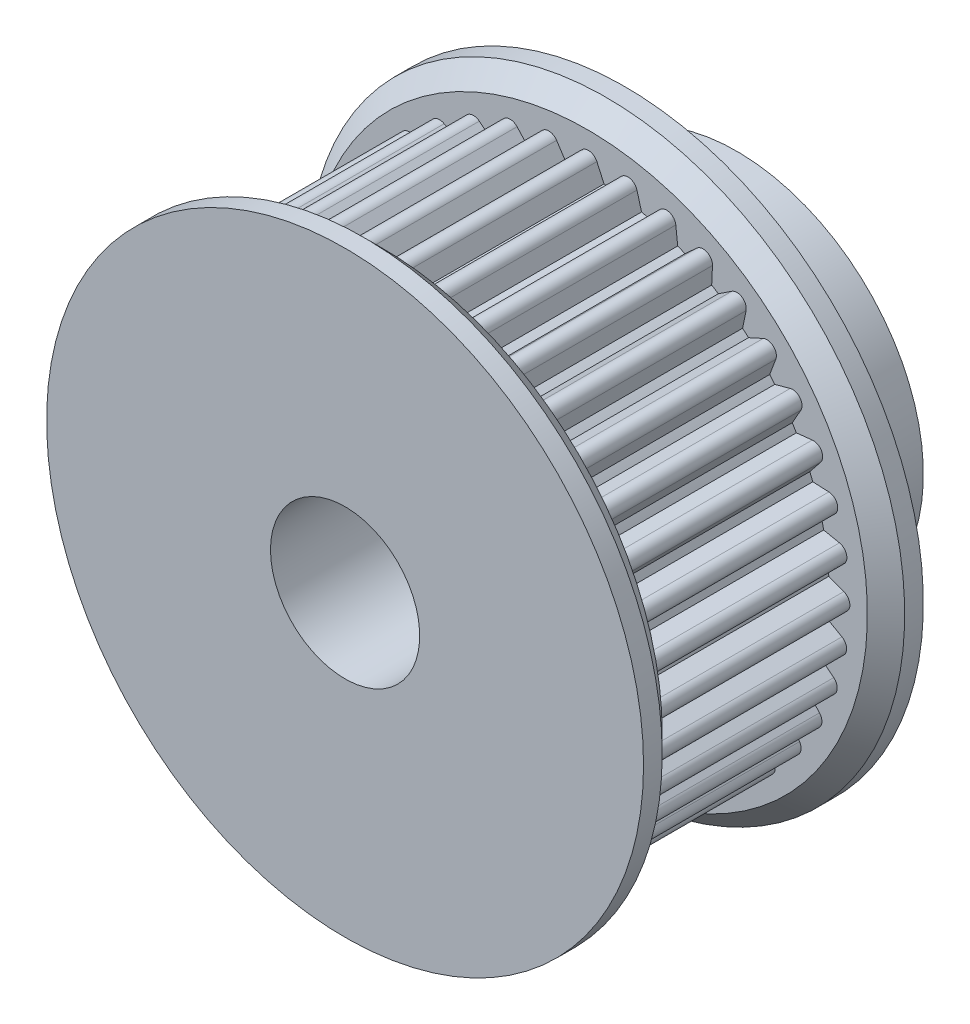
SolidWorks part; units mm, degrees
ref_plane "前视基准面" through (0, 0, 0) normal (0, 0, 1) x (1, 0, 0)
ref_plane "上视基准面" through (0, 0, 0) normal (0, 1, 0) x (1, 0, 0)
ref_plane "右视基准面" through (0, 0, 0) normal (1, 0, 0) x (0, 0, -1)
sketch "草图1" plane through (0, 0, 0) normal (0, 0, 1) x (1, 0, 0)
  line L0 (-0.7281, 12.9295) -> (0, 14.8658)
  line L1 (0, 14.8658) -> (0.8824, 12.9199)
  line L2 (0.8824, 12.9199) -> (-0.7281, 12.9295)
  line L3 (1.3035, 12.8842) -> (2.3255, 14.6827)
  line L4 (2.3255, 14.6827) -> (2.8926, 12.6228)
  line L5 (2.8926, 12.6228) -> (1.3035, 12.8842)
  line L6 (3.303, 12.5217) -> (4.5938, 14.1382)
  line L7 (4.5938, 14.1382) -> (4.8317, 12.0149)
  line L8 (4.8317, 12.0149) -> (3.303, 12.5217)
  line L9 (5.2212, 11.8508) -> (6.7489, 13.2455)
  line L10 (6.7489, 13.2455) -> (6.6517, 11.1111)
  line L11 (6.6517, 11.1111) -> (5.2212, 11.8508)
  line L12 (7.0108, 10.8881) -> (8.7379, 12.0266)
  line L13 (8.7379, 12.0266) -> (8.308, 9.9338)
  line L14 (8.308, 9.9338) -> (7.0108, 10.8881)
  line L15 (8.6277, 9.6574) -> (10.5117, 10.5117)
  line L16 (10.5117, 10.5117) -> (9.7597, 8.5118)
  line L17 (9.7597, 8.5118) -> (8.6277, 9.6574)
  line L18 (10.0323, 8.1888) -> (12.0266, 8.7379)
  line L19 (12.0266, 8.7379) -> (10.9711, 6.8803)
  line L20 (10.9711, 6.8803) -> (10.0323, 8.1888)
  line L21 (11.1897, 6.5186) -> (13.2455, 6.7489)
  line L22 (13.2455, 6.7489) -> (11.9123, 5.0793)
  line L23 (11.9123, 5.0793) -> (11.1897, 6.5186)
  line L24 (12.0717, 4.6879) -> (14.1382, 4.5938)
  line L25 (14.1382, 4.5938) -> (12.5602, 3.1533)
  line L26 (12.5602, 3.1533) -> (12.0717, 4.6879)
  line L27 (12.6564, 2.7417) -> (14.6827, 2.3255)
  line L28 (14.6827, 2.3255) -> (12.8989, 1.1496)
  line L29 (12.8989, 1.1496) -> (12.6564, 2.7417)
  line L30 (12.9295, 0.7281) -> (14.8658, 0)
  line L31 (14.8658, 0) -> (12.9199, -0.8824)
  line L32 (12.9199, -0.8824) -> (12.9295, 0.7281)
  line L33 (12.8842, -1.3035) -> (14.6827, -2.3255)
  line L34 (14.6827, -2.3255) -> (12.6228, -2.8926)
  line L35 (12.6228, -2.8926) -> (12.8842, -1.3035)
  line L36 (12.5217, -3.303) -> (14.1382, -4.5938)
  line L37 (14.1382, -4.5938) -> (12.0149, -4.8317)
  line L38 (12.0149, -4.8317) -> (12.5217, -3.303)
  line L39 (11.8508, -5.2212) -> (13.2455, -6.7489)
  line L40 (13.2455, -6.7489) -> (11.1111, -6.6517)
  line L41 (11.1111, -6.6517) -> (11.8508, -5.2212)
  line L42 (10.8881, -7.0108) -> (12.0266, -8.7379)
  line L43 (12.0266, -8.7379) -> (9.9338, -8.308)
  line L44 (9.9338, -8.308) -> (10.8881, -7.0108)
  line L45 (9.6574, -8.6277) -> (10.5117, -10.5117)
  line L46 (10.5117, -10.5117) -> (8.5118, -9.7597)
  line L47 (8.5118, -9.7597) -> (9.6574, -8.6277)
  line L48 (8.1888, -10.0323) -> (8.7379, -12.0266)
  line L49 (8.7379, -12.0266) -> (6.8803, -10.9711)
  line L50 (6.8803, -10.9711) -> (8.1888, -10.0323)
  line L51 (6.5186, -11.1897) -> (6.7489, -13.2455)
  line L52 (6.7489, -13.2455) -> (5.0793, -11.9123)
  line L53 (5.0793, -11.9123) -> (6.5186, -11.1897)
  line L54 (4.6879, -12.0717) -> (4.5938, -14.1382)
  line L55 (4.5938, -14.1382) -> (3.1533, -12.5602)
  line L56 (3.1533, -12.5602) -> (4.6879, -12.0717)
  line L57 (2.7417, -12.6564) -> (2.3255, -14.6827)
  line L58 (2.3255, -14.6827) -> (1.1496, -12.8989)
  line L59 (1.1496, -12.8989) -> (2.7417, -12.6564)
  line L60 (0.7281, -12.9295) -> (0, -14.8658)
  line L61 (0, -14.8658) -> (-0.8824, -12.9199)
  line L62 (-0.8824, -12.9199) -> (0.7281, -12.9295)
  line L63 (-1.3035, -12.8842) -> (-2.3255, -14.6827)
  line L64 (-2.3255, -14.6827) -> (-2.8926, -12.6228)
  line L65 (-2.8926, -12.6228) -> (-1.3035, -12.8842)
  line L66 (-3.303, -12.5217) -> (-4.5938, -14.1382)
  line L67 (-4.5938, -14.1382) -> (-4.8317, -12.0149)
  line L68 (-4.8317, -12.0149) -> (-3.303, -12.5217)
  line L69 (-5.2212, -11.8508) -> (-6.7489, -13.2455)
  line L70 (-6.7489, -13.2455) -> (-6.6517, -11.1111)
  line L71 (-6.6517, -11.1111) -> (-5.2212, -11.8508)
  line L72 (-7.0108, -10.8881) -> (-8.7379, -12.0266)
  line L73 (-8.7379, -12.0266) -> (-8.308, -9.9338)
  line L74 (-8.308, -9.9338) -> (-7.0108, -10.8881)
  line L75 (-8.6277, -9.6574) -> (-10.5117, -10.5117)
  line L76 (-10.5117, -10.5117) -> (-9.7597, -8.5118)
  line L77 (-9.7597, -8.5118) -> (-8.6277, -9.6574)
  line L78 (-10.0323, -8.1888) -> (-12.0266, -8.7379)
  line L79 (-12.0266, -8.7379) -> (-10.9711, -6.8803)
  line L80 (-10.9711, -6.8803) -> (-10.0323, -8.1888)
  line L81 (-11.1897, -6.5186) -> (-13.2455, -6.7489)
  line L82 (-13.2455, -6.7489) -> (-11.9123, -5.0793)
  line L83 (-11.9123, -5.0793) -> (-11.1897, -6.5186)
  line L84 (-12.0717, -4.6879) -> (-14.1382, -4.5938)
  line L85 (-14.1382, -4.5938) -> (-12.5602, -3.1533)
  line L86 (-12.5602, -3.1533) -> (-12.0717, -4.6879)
  line L87 (-12.6564, -2.7417) -> (-14.6827, -2.3255)
  line L88 (-14.6827, -2.3255) -> (-12.8989, -1.1496)
  line L89 (-12.8989, -1.1496) -> (-12.6564, -2.7417)
  line L90 (-12.9295, -0.7281) -> (-14.8658, 0)
  line L91 (-14.8658, 0) -> (-12.9199, 0.8824)
  line L92 (-12.9199, 0.8824) -> (-12.9295, -0.7281)
  line L93 (-12.8842, 1.3035) -> (-14.6827, 2.3255)
  line L94 (-14.6827, 2.3255) -> (-12.6228, 2.8926)
  line L95 (-12.6228, 2.8926) -> (-12.8842, 1.3035)
  line L96 (-12.5217, 3.303) -> (-14.1382, 4.5938)
  line L97 (-14.1382, 4.5938) -> (-12.0149, 4.8317)
  line L98 (-12.0149, 4.8317) -> (-12.5217, 3.303)
  line L99 (-11.8508, 5.2212) -> (-13.2455, 6.7489)
  line L100 (-13.2455, 6.7489) -> (-11.1111, 6.6517)
  line L101 (-11.1111, 6.6517) -> (-11.8508, 5.2212)
  line L102 (-10.8881, 7.0108) -> (-12.0266, 8.7379)
  line L103 (-12.0266, 8.7379) -> (-9.9338, 8.308)
  line L104 (-9.9338, 8.308) -> (-10.8881, 7.0108)
  line L105 (-9.6574, 8.6277) -> (-10.5117, 10.5117)
  line L106 (-10.5117, 10.5117) -> (-8.5118, 9.7597)
  line L107 (-8.5118, 9.7597) -> (-9.6574, 8.6277)
  line L108 (-8.1888, 10.0323) -> (-8.7379, 12.0266)
  line L109 (-8.7379, 12.0266) -> (-6.8803, 10.9711)
  line L110 (-6.8803, 10.9711) -> (-8.1888, 10.0323)
  line L111 (-6.5186, 11.1897) -> (-6.7489, 13.2455)
  line L112 (-6.7489, 13.2455) -> (-5.0793, 11.9123)
  line L113 (-5.0793, 11.9123) -> (-6.5186, 11.1897)
  line L114 (-4.6879, 12.0717) -> (-4.5938, 14.1382)
  line L115 (-4.5938, 14.1382) -> (-3.1533, 12.5602)
  line L116 (-3.1533, 12.5602) -> (-4.6879, 12.0717)
  line L117 (-2.7417, 12.6564) -> (-2.3255, 14.6827)
  line L118 (-2.3255, 14.6827) -> (-1.1496, 12.8989)
  line L119 (-1.1496, 12.8989) -> (-2.7417, 12.6564)
  circle A0 centre (0, 0) radius 12.95
  point P125 (0, 0)
  dimension "D1" = 25.9
  dimension "D2" = 40
extrude "凸台-拉伸3" add sketch "草图1" along normal blind 11 contours L32 A0 L29 L26 L23 L20 L17 L14 L11 L8 L5 L2 L119 L116 L113 L110 L107 L104 L101 L98 L95 L92 L89 L86 L83 L80 L77 | L72 L73 L74 | L69 L70 L71 | L66 L67 L68 | L63 L64 L65 | L60 L61 L62 | L57 L58 L59 | L54 L55 L56 | L49 L50 L48 | L52 L53 L51 | L46 L47 L45 | L43 L44 L42 | L40 L41 L39 | L37 L38 L36 | L33 L34 L35
fillet "圆角3" radius 0.5 40 edges at (-10.5117, 10.5117, 5.5) (-12.0266, 8.7379, 5.5) (-13.2455, 6.7489, 5.5) (-14.1382, 4.5938, 5.5) (-14.6827, 2.3255, 5.5) (-14.8658, 0, 5.5) (-14.6827, -2.3255, 5.5) (-14.1382, -4.5938, 5.5) (-13.2455, -6.7489, 5.5) (-12.0266, -8.7379, 5.5) (-10.5117, -10.5117, 5.5) (-8.7379, -12.0266, 5.5) (-6.7489, -13.2455, 5.5) (-4.5938, -14.1382, 5.5) (-2.3255, -14.6827, 5.5) (0, -14.8658, 5.5) (2.3255, -14.6827, 5.5) (4.5938, -14.1382, 5.5) (6.7489, -13.2455, 5.5) (8.7379, -12.0266, 5.5) (10.5117, -10.5117, 5.5) (12.0266, -8.7379, 5.5) (13.2455, -6.7489, 5.5) (14.1382, -4.5938, 5.5) (14.6827, -2.3255, 5.5) (14.8658, 0, 5.5) (14.6827, 2.3255, 5.5) (14.1382, 4.5938, 5.5) (13.2455, 6.7489, 5.5) (12.0266, 8.7379, 5.5) (10.5117, 10.5117, 5.5) (8.7379, 12.0266, 5.5) (6.7489, 13.2455, 5.5) (4.5938, 14.1382, 5.5) (2.3255, 14.6827, 5.5) (0, 14.8658, 5.5) (-2.3255, 14.6827, 5.5) (-4.5938, 14.1382, 5.5) (-6.7489, 13.2455, 5.5) (-8.7379, 12.0266, 5.5)
sketch "草图3" plane through (0, 0, 11) normal (0, 0, 1) x (1, 0, 0)
  circle A0 centre (0, 0) radius 16
  dimension "D1" = 32
extrude "凸台-拉伸4" add sketch "草图3" along normal blind 2
sketch "草图4" plane through (0, 0, 0) normal (0, 0, -1) x (-1, 0, 0)
  circle A0 centre (0, 0) radius 16
  dimension "D1" = 32
extrude "凸台-拉伸5" add sketch "草图4" along normal blind 2
chamfer "倒角1" distance 1 angle 45 1 edges at (16, 0, 11)
chamfer "倒角2" distance 1 angle 45 1 edges at (-16, 0, 0)
sketch "草图5" plane through (0, 0, -2) normal (0, 0, -1) x (-1, 0, 0)
  circle A0 centre (0, 0) radius 10
  dimension "D1" = 20
extrude "凸台-拉伸6" add sketch "草图5" along normal blind 6
sketch "草图6" plane through (0, 0, -8) normal (0, 0, -1) x (-1, 0, 0)
  circle A0 centre (0, 0) radius 4
  dimension "D1" = 8
extrude "切除-拉伸1" cut sketch "草图6" against normal through all
ref_plane "基准面1" through (0, 10, 0) normal (0, 1, 0) x (1, 0, 0)
hole_wizard "#5-44 螺纹孔1" positions "3D草图1" profile "草图8" tap size "#5-44" standard "ANSI Inch"
sketch3d "3D草图1"
  point P0 (0.017, 10, -4.9601)
sketch "草图8" plane through (0.017, 10, -4.9601) normal (0, 0, 1) x (-1, 0.0017, 0)
  line L0 (0, 0) -> (0, 6)
  line L1 (0, 6) -> (1.3208, 6)
  line L2 (1.3208, 6) -> (1.3208, 0)
  line L5 (1.3208, 0) -> (0, 0)
  line L11 (0, -6.35) -> (0, 107.95) construction
  dimension "通孔螺纹孔钻头直径" = 2.6416
  dimension "通孔螺纹孔钻头深度" = 6
cosmetic thread "孔螺蚊线1" parameters "D2"=3.175
hole_wizard "#5-44 螺纹孔2" positions "3D草图2" profile "草图9" tap size "#5-44" standard "ANSI Inch"
sketch3d "3D草图2"
  point P0 (9.937, -1.1209, -5.2383)
  point P1 (8.3819, -5.4538, -5.1149)
sketch "草图9" plane through (8.3819, -5.4538, -5.1149) normal (0, 0, 1) x (0.5454, 0.8382, 0)
  line L0 (0, 0) -> (0, 10)
  line L1 (0, 10) -> (1.3208, 10)
  line L2 (1.3208, 10) -> (1.3208, 0)
  line L5 (1.3208, 0) -> (0, 0)
  line L11 (0, -6.35) -> (0, 107.95) construction
  dimension "通孔螺纹孔钻头直径" = 2.6416
  dimension "通孔螺纹孔钻头深度" = 10
cosmetic thread "孔螺蚊线2" parameters "D2"=3.175
